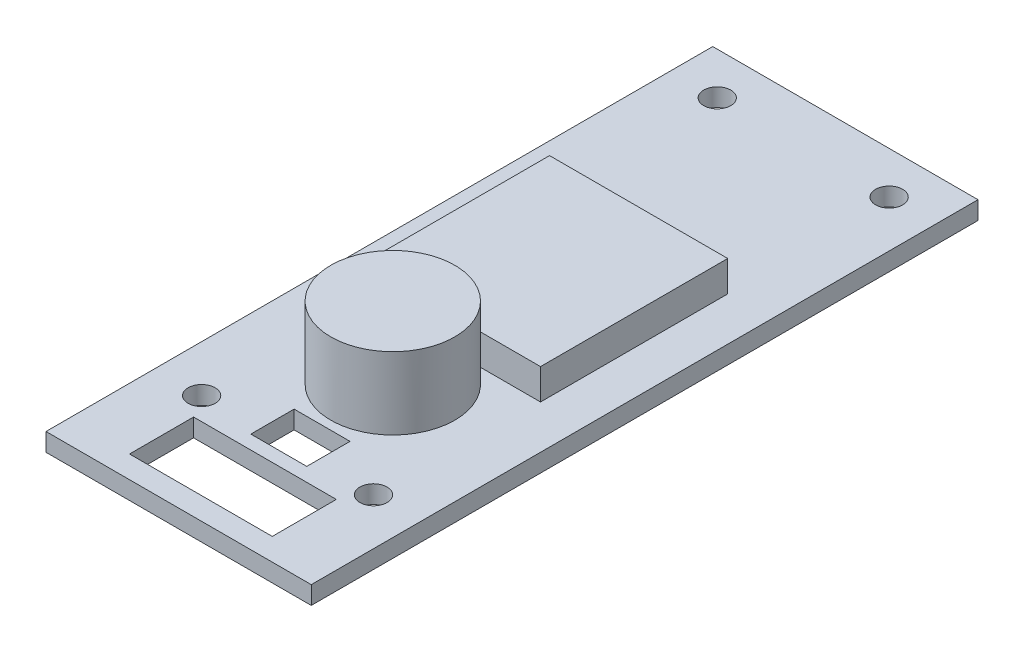
SolidWorks part; units mm, degrees
note: The reader was unsure of these and kept them because the rebuilt part matched: shared geometry of "Sketch1<3>", "Sketch1<4>".
ref_plane "Front Plane" through (0, 0, 0) normal (0, 0, 1) x (1, 0, 0)
ref_plane "Top Plane" through (0, 0, 0) normal (0, 1, 0) x (1, 0, 0)
ref_plane "Right Plane" through (0, 0, 0) normal (1, 0, 0) x (0, 0, -1)
sketch "Sketch1" plane through (0, 0, 0) normal (0, 1, 0) x (1, 0, 0)
  line L0 (0, 3.661) -> (0, 0) construction
  line L1 (12.7, -34.95) -> (-12.7, -34.95)
  line L2 (12.7, -34.95) -> (12.7, 34.95)
  line L3 (12.7, 34.95) -> (-12.7, 34.95)
  line L4 (-12.7, -34.95) -> (-12.7, 34.95)
  line L5 (12.7, -34.95) -> (-12.7, 34.95) construction
  line L6 (12.7, 34.95) -> (-12.7, -34.95) construction
  line L7 (8.875, 13.036) -> (-8.875, 13.036)
  line L8 (8.875, 13.036) -> (8.875, -5.714)
  line L9 (8.875, -5.714) -> (-8.875, -5.714)
  line L10 (-8.875, 13.036) -> (-8.875, -5.714)
  line L11 (8.875, 13.036) -> (-8.875, -5.714) construction
  line L12 (8.875, -5.714) -> (-8.875, 13.036) construction
  line L13 (0, -13.214) -> (0, 0) construction
  line L14 (0, -23.449) -> (0, -34.95) construction
  line L15 (3, -25.749) -> (-3, -25.749)
  line L16 (3, -25.749) -> (3, -21.149)
  line L17 (3, -21.149) -> (-3, -21.149)
  line L18 (-3, -25.749) -> (-3, -21.149)
  line L19 (3, -25.749) -> (-3, -21.149) construction
  line L20 (3, -21.149) -> (-3, -25.749) construction
  line L21 (9.875, 14.036) -> (9.875, -6.714)
  line L22 (-7.81, -27.482) -> (7.81, -27.482)
  line L23 (-7.81, -27.482) -> (-7.81, -34.382)
  line L24 (-7.81, -34.382) -> (7.81, -34.382)
  line L25 (7.81, -27.482) -> (7.81, -34.382)
  line L26 (-7.81, -27.482) -> (7.81, -34.382) construction
  line L27 (-7.81, -34.382) -> (7.81, -27.482) construction
  line L28 (9.875, -6.714) -> (-9.875, -6.714)
  line L29 (-9.875, 14.036) -> (-9.875, -6.714)
  line L30 (9.875, 14.036) -> (-9.875, 14.036)
  line L31 (3.1, -25.849) -> (3.1, -21.049)
  line L32 (3.1, -21.049) -> (-3.1, -21.049)
  line L33 (-3.1, -25.849) -> (-3.1, -21.049)
  line L34 (3.1, -25.849) -> (-3.1, -25.849)
  line L35 (-7.91, -27.382) -> (-7.91, -34.482)
  line L36 (-7.91, -34.482) -> (7.91, -34.482)
  line L37 (7.91, -27.382) -> (7.91, -34.482)
  line L38 (-7.91, -27.382) -> (7.91, -27.382)
  line L39 (14.7, -36.95) -> (14.7, 36.95)
  line L40 (14.7, 36.95) -> (-14.7, 36.95)
  line L41 (-14.7, -36.95) -> (-14.7, 36.95)
  line L42 (14.7, -36.95) -> (-14.7, -36.95)
  circle A0 centre (0, -13.214) radius 5.875
  circle A1 centre (0, -13.214) radius 6.875
  point P0 (0, 0)
  point P8 (0, 3.661)
  point P15 (0, -23.449)
  point P22 (0, -30.932)
  dimension "D1" = 11.75
  dimension "D7" = 7.5
  dimension "D2" = 18.75
  dimension "D3" = 17.75
  dimension "D4" = 25.4
  dimension "D5" = 21.914
  dimension "D6" = 6.9
  dimension "D8" = 6
  dimension "D9" = 4.6
  dimension "D10" = 7.935
  dimension "D11" = 15.62
  dimension "D12" = 1.733
  dimension "D13" = 69.9
  dimension "D14" = 1
  dimension "D15" = 1
  dimension "D16" = 0.1
  dimension "D17" = 0.1
  dimension "D18" = 2
extrude "Boss-Extrude1" add sketch "Sketch1" along normal blind 2 contours L4 L1 L2 L3 A1 L31 L34 L33 L32 L30 L21 L28 L29 L35 L38 L37 L36 | L42 L39 L40 L41 L1 L4 L3 L2
extrude "Boss-Extrude2" add sketch "Sketch1<3>" along normal blind 10 separate body contours A1
sketch "Sketch1<3>" plane through (0, 0, 0) normal (0, 1, 0) x (1, 0, 0) same geometry as "Sketch1"
shell "Shell1" thickness 0.75
extrude "Boss-Extrude3" add sketch "Sketch1<4>" along normal blind 5.4 contours A1 L28 L21 L30 L29 L10 L7 L8 L9 | L7 L10 L9 L8
sketch "Sketch1<4>" plane through (0, 0, 0) normal (0, 1, 0) x (1, 0, 0) same geometry as "Sketch1"
sketch "Sketch2" plane through (0, 0, 0) normal (0, -1, 0) x (1, 0, 0)
  line L0 (8.875, 5.714) -> (-8.875, -13.036) construction
  line L1 (9.5, -13.161) -> (-9.5, -13.161)
  line L2 (9.5, -13.161) -> (9.5, 5.839)
  line L3 (9.5, 5.839) -> (-9.5, 5.839)
  line L4 (-9.5, -13.161) -> (-9.5, 5.839)
  line L5 (9.5, -13.161) -> (-9.5, 5.839) construction
  line L6 (9.5, 5.839) -> (-9.5, -13.161) construction
  point P0 (0, -3.661)
  dimension "D1" = 19
  dimension "D2" = 19
extrude "Cut-Extrude1" cut sketch "Sketch2" against normal offset from surface (4.4 mm away) 1 up to face at (0, 5.4, -0.2652)
sketch "Sketch3" plane through (0, 2, 0) normal (0, 1, 0) x (1, 0, 0)
  line L0 (-14.7, -36.95) -> (-14.7, 36.95) construction
  line L1 (12.7, -34.4) -> (-12.7, -34.4)
  line L2 (12.7, -34.4) -> (12.7, 35.45)
  line L3 (12.7, 35.45) -> (-12.7, 35.45)
  line L4 (-12.7, -34.4) -> (-12.7, 35.45)
  line L5 (12.7, -34.4) -> (-12.7, 35.45) construction
  line L6 (12.7, 35.45) -> (-12.7, -34.4) construction
  line L7 (-9.525, 32.275) -> (9.525, 32.275)
  line L8 (-9.525, 32.275) -> (-9.525, -24.875)
  line L9 (-9.525, -24.875) -> (9.525, -24.875)
  line L10 (9.525, 32.275) -> (9.525, -24.875)
  line L11 (14.7, 36.95) -> (-14.7, 36.95) construction
  circle A0 centre (-9.525, 32.275) radius 1.5
  circle A1 centre (9.525, 32.275) radius 1.5
  circle A2 centre (9.525, -24.875) radius 1.5
  circle A3 centre (-9.525, -24.875) radius 1.5
  point P0 (0, 0)
  point P14 (0, 0)
  dimension "D7" = 3
  dimension "D1" = 25.4
  dimension "D2" = 69.85
  dimension "D3" = 3.175
  dimension "D4" = 3.175
  dimension "D5" = 3.175
  dimension "D6" = 9.525
  dimension "D8" = 2
  dimension "D9" = 1.5
extrude "Cut-Extrude2" cut sketch "Sketch3" against normal through all both and the other way through all contours L7 A0 L8 | L8 A0 L7 | L10 A1 L7 | L7 A1 L10 | L9 A2 L10 | L10 A2 L9 | L8 A3 L9 | L9 A3 L8
